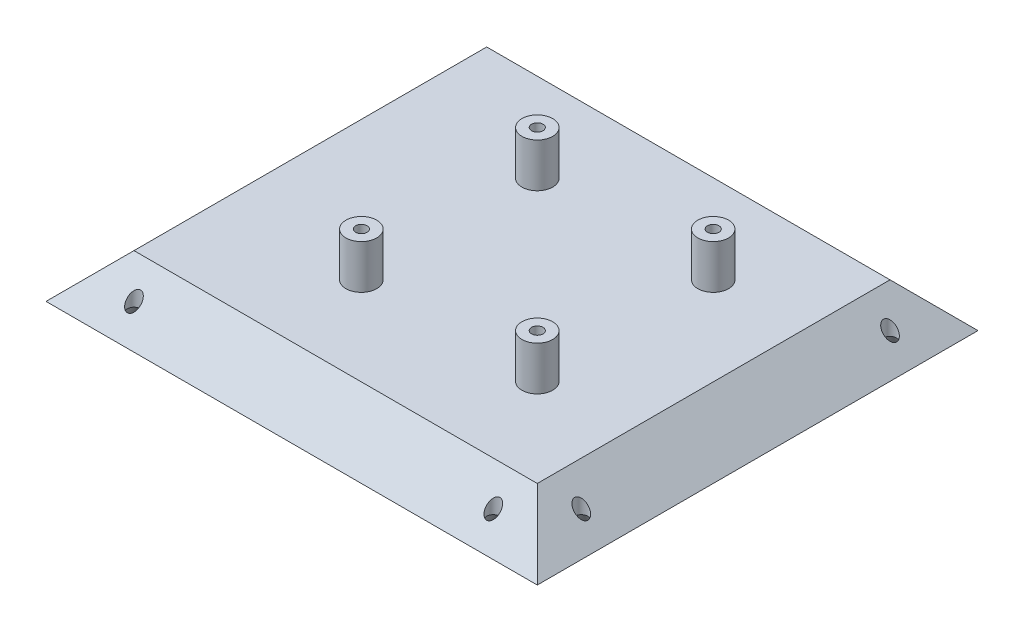
SolidWorks part; units mm, degrees
ref_plane "Спереди" through (0, 0, 0) normal (0, 0, 1) x (1, 0, 0)
ref_plane "Сверху" through (0, 0, 0) normal (0, 1, 0) x (1, 0, 0)
ref_plane "Справа" through (0, 0, 0) normal (1, 0, 0) x (0, 0, -1)
sketch "Sketch1" plane through (0, 0, 0) normal (0, 1, 0) x (1, 0, 0)
  line L1 (0, 0) -> (111.7, 0)
  line L2 (0, 0) -> (0, -100.2)
  line L3 (0, -100.2) -> (111.7, -100.2)
  line L4 (111.7, 0) -> (111.7, -100.2)
  dimension "D1" = 111.7
  dimension "D2" = 100.2
ref_plane "Plane1" through (0, 10, 0) normal (0, 1, 0) x (1, 0, 0)
sketch "Sketch2" plane through (0, 10, 0) normal (0, 1, 0) x (1, 0, 0)
  line L8 (10, -10) -> (10, -90.2)
  line L9 (101.7, -10) -> (10, -10)
  line L10 (101.7, -90.2) -> (101.7, -10)
  line L11 (10, -90.2) -> (101.7, -90.2)
  line L12 (10, -10) -> (10, -90.2)
  line L13 (101.7, -10) -> (10, -10)
  line L14 (101.7, -90.2) -> (101.7, -10)
  line L15 (10, -90.2) -> (101.7, -90.2)
  dimension "D1" = 10
loft "Loft1" add profiles "Sketch1", "Sketch2" connector at (0, 0, 100.2) connector at (10, 10, 90.2)
sketch "Sketch3" plane through (0, 0, 0) normal (0, -1, 0) x (1, 0, 0)
  line L0 (10, 10) -> (101.7, 10) construction
  line L1 (0, 0) -> (111.7, 0) construction
  line L2 (0, 0) -> (0, 100.2) construction
  line L3 (0, 100.2) -> (111.7, 100.2) construction
  line L4 (111.7, 0) -> (111.7, 100.2) construction
  line L5 (101.7, 10) -> (101.7, 90.2) construction
  line L6 (10, 90.2) -> (101.7, 90.2) construction
  line L7 (10, 10) -> (10, 90.2) construction
  line L8 (10, 10) -> (5, 10) construction
  line L9 (5, 10) -> (5, 15) construction
  line L10 (5, 15) -> (5, 20) construction
  line L11 (5, 20) -> (10, 20) construction
  line L12 (5, 15) -> (0, 15) construction
  line L13 (5, 15) -> (10, 15) construction
  line L14 (55.85, 0) -> (55.85, 100.2) construction
  line L15 (0, 50.1) -> (111.7, 50.1) construction
  line L16 (0, 0) -> (10, 10) construction
  circle A0 centre (5, 15) radius 1.5
  circle A1 centre (5, 85.2) radius 1.5
  circle A2 centre (106.7, 85.2) radius 1.5
  circle A3 centre (106.7, 15) radius 1.5
  circle A4 centre (15, 5) radius 1.5
  circle A5 centre (15, 95.2) radius 1.5
  circle A6 centre (96.7, 95.2) radius 1.5
  circle A7 centre (96.7, 5) radius 1.5
  dimension "D2" = 3
  dimension "D3" = 10
  dimension "D1" = 10
extrude "Cut-Extrude1" cut sketch "Sketch3" against normal through all
sketch "Sketch4" plane through (0, 10, 0) normal (0, 1, 0) x (1, 0, 0)
  line L0 (61.6, -90.2) -> (101.7, -90.2) construction
  line L1 (10, -90.2) -> (101.7, -90.2) construction
  line L2 (81.6, -70.1) -> (101.7, -70.1) construction
  line L3 (101.7, -90.2) -> (101.7, -10) construction
  line L4 (101.7, -50.1) -> (10, -50.1) construction
  line L5 (10, -10) -> (10, -90.2) construction
  line L6 (55.85, -90.2) -> (55.85, -10) construction
  line L7 (101.7, -10) -> (10, -10) construction
  line L8 (21.5, -10) -> (21.5, -90.2) construction
  line L9 (61.6, -90.2) -> (61.6, -10) construction
  line L10 (21.5, -90.2) -> (61.6, -90.2) construction
  line L11 (41.6, -30.1) -> (61.6, -30.1) construction
  line L12 (61.6, -30.1) -> (81.6, -30.1) construction
  circle A0 centre (81.6, -70.1) radius 1.3
  circle A1 centre (81.6, -70.1) radius 3.5
  circle A2 centre (81.6, -30.1) radius 3.5
  circle A3 centre (81.6, -30.1) radius 1.3
  circle A12 centre (41.6, -70.1) radius 3.5
  circle A13 centre (41.6, -70.1) radius 1.3
  circle A14 centre (41.6, -30.1) radius 1.3
  circle A15 centre (41.6, -30.1) radius 3.5
  dimension "D1" = 2.6
  dimension "D4" = 80.2
  dimension "D2" = 7
  dimension "D3" = 40
  dimension "D5" = 40
extrude "Boss-Extrude1" add sketch "Sketch4" along normal blind 10
sketch "Sketch5" plane through (0, 0, 0) normal (0, -1, 0) x (1, 0, 0)
  line L1 (111.7, 50.1) -> (0, 50.1) construction
  line L2 (111.7, 100.2) -> (111.7, 0) construction
  line L3 (0, 0) -> (0, 100.2) construction
  line L4 (55.85, 100.2) -> (55.85, 0) construction
  line L5 (0, 100.2) -> (111.7, 100.2) construction
  line L6 (111.7, 0) -> (0, 0) construction
  line L7 (111.7, 100.2) -> (101.7, 90.2) construction
  circle A0 centre (106.7, 85.2) radius 3.3
  dimension "D1" = 6.6
  dimension "D2" = 10
  dimension "D3" = 10
ref_plane "Plane2" through (0, 2.8, 0) normal (0, -1, 0) x (-1, 0, 0)
sketch "Sketch6" plane through (0, 2.8, 0) normal (0, -1, 0) x (-1, 0, 0)
  line L2 (-55.85, -100.2) -> (-55.85, 0) construction
  line L3 (-55.85, -100.2) -> (-55.85, 0) construction
  line L4 (-111.7, -50.1) -> (0, -50.1) construction
  line L5 (-111.7, -50.1) -> (0, -50.1) construction
  line L6 (-111.7, -100.2) -> (-101.7, -90.2) construction
  line L7 (-111.7, -100.2) -> (-101.7, -90.2) construction
  circle A0 centre (-106.7, -85.2) radius 1.5 construction
  circle A1 centre (-106.7, -85.2) radius 1.5
ref_plane "Plane3" through (55.85, 0, 0) normal (-1, 0, 0) x (0, 0, 1)
ref_plane "Plane5" through (0, 0, 50.1) normal (0, 0, -1) x (-1, 0, 0)
loft "Cut-Loft1" cut profiles "Sketch5", "Sketch6" connector at (109.6008, 0, 86.7734) connector at (108.0237, 2.8, 85.9055)
ref_plane "Plane6" through (5.75, 0, -5.75) normal (0.7071, 0, -0.7071) x (-0.7071, 0, -0.7071)
mirror "Mirror1" about plane through (5.75, 0, -5.75) normal (0.7071, 0, -0.7071) of "Cut-Loft1"
mirror "Mirror2" about plane through (0, 0, 50.1) normal (0, 0, -1) of "Mirror1", "Cut-Loft1"
mirror "Mirror3" about plane through (55.85, 0, 0) normal (-1, 0, 0) of "Mirror2", "Mirror1", "Cut-Loft1"
